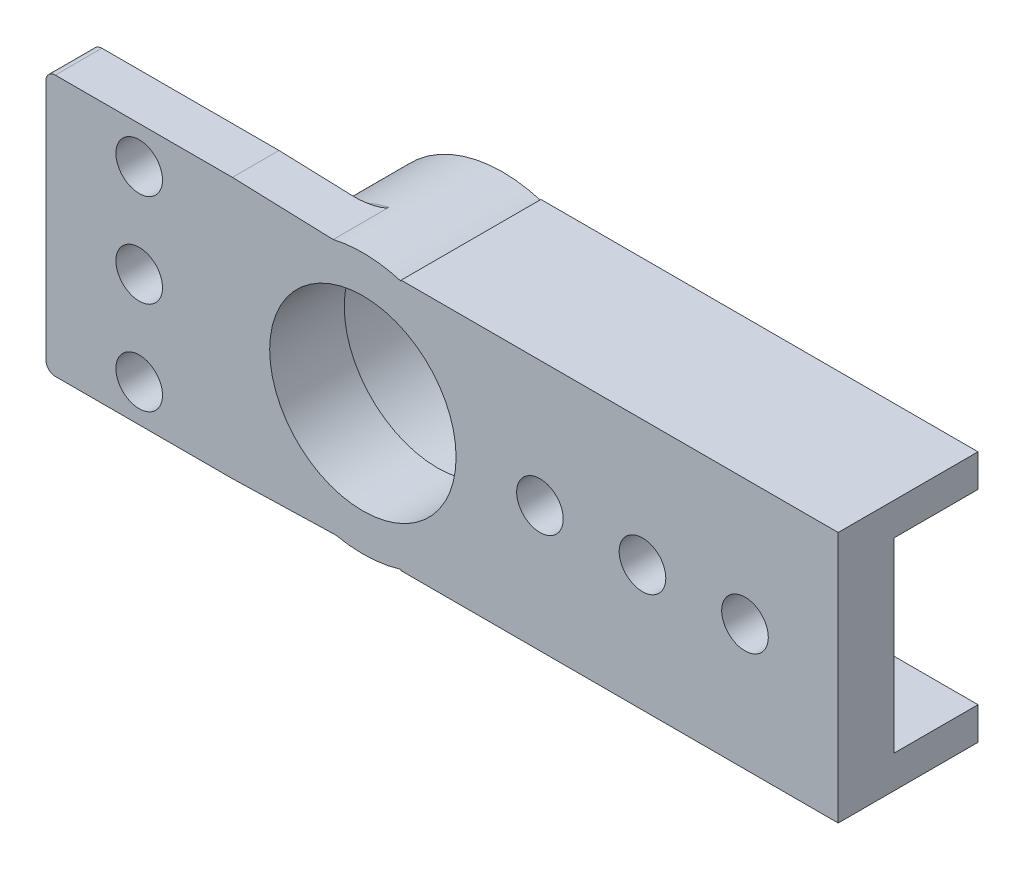
SolidWorks part; units mm, degrees
ref_plane "前视基准面" through (0, 0, 0) normal (0, 0, 1) x (1, 0, 0)
ref_plane "上视基准面" through (0, 0, 0) normal (0, 1, 0) x (1, 0, 0)
ref_plane "右视基准面" through (0, 0, 0) normal (1, 0, 0) x (0, 0, -1)
sketch "草图1" plane through (0, 0, 0) normal (0, 0, 1) x (1, 0, 0)
  line L1 (20, -10) -> (-20, -10)
  line L2 (20, -10) -> (20, 10)
  line L3 (20, 10) -> (-20, 10)
  line L4 (-20, -10) -> (-20, 10)
  line L5 (20, -10) -> (-20, 10) construction
  line L6 (20, 10) -> (-20, -10) construction
  point P0 (0, 0)
  dimension "D1" = 40
  dimension "D2" = 20
extrude "凸台-拉伸1" add sketch "草图1" along normal blind 6
sketch "草图2" plane through (0, 0, 6) normal (0, 0, 1) x (1, 0, 0)
  line L0 (20, -10) -> (20, 10) construction
  circle A0 centre (10, 0) radius 2.5
  circle A1 centre (-1, 0) radius 2.5
  circle A2 centre (-12, 0) radius 2.5
  dimension "D1" = 10
  dimension "D2" = 5
  dimension "D3" = 3
extrude "切除-拉伸1" cut sketch "草图2" against normal through all
sketch "草图3" plane through (0, 0, 6) normal (0, 0, 1) x (1, 0, 0)
  line L0 (20, 13.5) -> (20, 10)
  line L1 (20, -13.5) -> (-26.894, -13.5)
  line L3 (20, 13.5) -> (-26.894, 13.5)
  line L4 (-20, 10) -> (-20, -10)
  line L5 (-20, -10) -> (20, -10)
  line L6 (20, -10) -> (20, 10)
  line L7 (20, 10) -> (-20, 10)
  line L8 (-20, 10) -> (-20, -10)
  line L9 (-20, -10) -> (20, -10)
  line L10 (20, -10) -> (20, 10)
  line L11 (20, 10) -> (-20, 10)
  line L12 (-26.894, -13.5) -> (-26.894, 13.5)
  line L13 (20, -10.0394) -> (-26.894, 13.5) construction
  line L14 (20, 10.0394) -> (-26.894, -13.5) construction
  line L15 (20, -10) -> (20, -13.5)
  circle A0 centre (-31, 0) radius 11
  circle A1 centre (-31, 0) radius 14
  point P2 (0, 0)
  line M10 (-20, 10) -> (-20, -10)
  line M11 (-20, -10) -> (20, -10)
  line M13 (20, 10) -> (-20, 10)
  dimension "D3" = 22
  dimension "D4" = 28
  dimension "D2" = 3.5
  dimension "D1" = 0
extrude "凸台-拉伸2" add sketch "草图3" against normal blind 15 contours L3 A1 L1 L12 A0 | A1 L1 L15 M11 M10 | L1 A1 L8 A0 L12 | L8 A1 L3 L12 A0 | L8 A1 | A1 L0 L3 M10 M13 region at (-1.9449, 11.7771, 6) region at (-1.9449, -11.7771, 6) region at (-23.0173, 9.0328, 6) region at (-27.2274, 11.7946, 6) region at (-18.7882, 0, 6) region at (-23.0173, -9.0328, 6)
sketch "草图5" plane through (0, 0, 6) normal (0, 0, 1) x (1, 0, 0)
  circle A0 centre (-31, 0) radius 10
  circle A1 centre (-31, 0) radius 11 construction
  circle A2 centre (-31, 0) radius 11
  dimension "D1" = 20
extrude "凸台-拉伸3" add sketch "草图5" against normal blind 8
sketch "草图6" plane through (0, 0, 6) normal (0, 0, 1) x (1, 0, 0)
  circle A0 centre (-31, 0) radius 8.5
  circle A1 centre (-31, 0) radius 10 construction
  circle A2 centre (-31, 0) radius 10
  dimension "D1" = 17
sketch "草图8" plane through (0, 0, 6) normal (0, 0, 1) x (1, 0, 0)
  line L0 (20, -13.5) -> (20, 13.5) construction
  line L1 (20, -13.5) -> (-26.894, -13.5) construction
  line L2 (20, 13.5) -> (-26.894, 13.5) construction
  line L3 (20, -13.5) -> (20, 13.5)
  line L4 (20, -13.5) -> (-26.894, -13.5)
  line L5 (20, 13.5) -> (-26.894, 13.5)
  line L6 (-45, -14) -> (-26.894, -13.5)
  line L7 (-45, -14) -> (-65, -14)
  line L8 (-45, -14) -> (-45, 14)
  line L9 (-45, 14) -> (-65, 14)
  line L10 (-65, -14) -> (-65, 14)
  line L11 (-45, -14) -> (-65, 14) construction
  line L12 (-45, 14) -> (-65, -14) construction
  line L13 (-45, 14) -> (-26.894, 13.3843)
  line L14 (-12, 0) -> (-31, 0)
  arc A0 (-26.894, 13.3843) -> (-26.894, -13.3843) centre (-31, 0) ccw construction
  arc A1 (-26.894, 13.3843) -> (-26.894, -13.3843) centre (-31, 0) ccw
  point P6 (-55, 0)
  arc M11 (-26.894, 13.3843) -> (-26.894, -13.3843) centre (-31, 0) ccw
  dimension "D1" = 28
  dimension "D2" = 20
  dimension "D3" = 14
extrude "凸台-拉伸4" add sketch "草图8" against normal blind 5 contours L10 L7 L8 L9 | L8 L6 M11 | L13 L8 M11 region at (-42.1177, -10.7223, 6) region at (-55, 0, 6) region at (-42.1603, 10.6928, 6)
fillet "圆角1" radius 1 1 edges at (-44.9993, -0.1411, 1)
fillet "圆角2" radius 1 2 edges at (-65, 14, 3.5) (-65, -14, 3.5)
sketch "草图9" plane through (0, 0, 6) normal (0, 0, 1) x (1, 0, 0)
  line L0 (-65, 0) -> (-55, 0) construction
  line L1 (-65, -13) -> (-65, 13) construction
  circle A0 centre (-55, 0) radius 2.5
  circle A1 centre (-55, 10) radius 2.5
  circle A2 centre (-55, -10) radius 2.5
  dimension "D2" = 2
  dimension "5" = 5
  dimension "D1" = 10
  dimension "D3" = 2
extrude "切除-拉伸2" cut sketch "草图9" against normal blind 5
